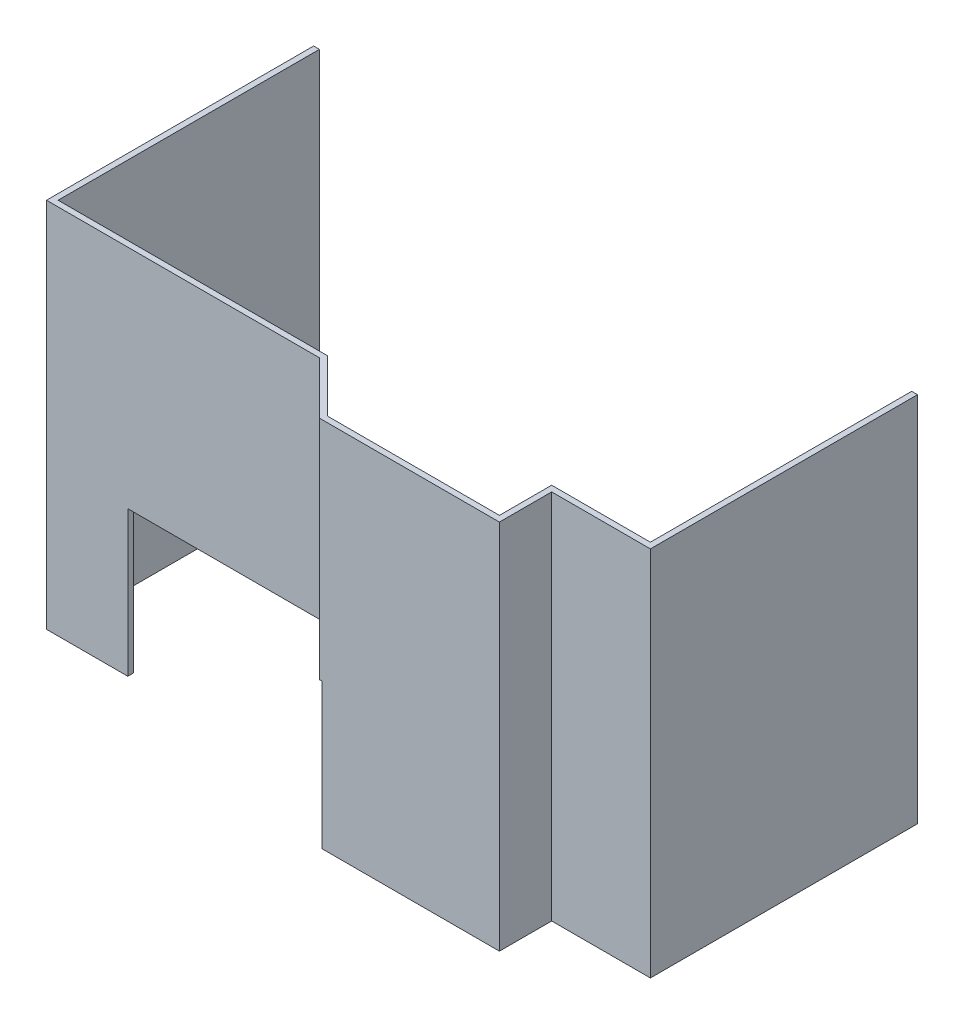
SolidWorks part; units mm, degrees
ref_plane "Front Plane" through (0, 0, 0) normal (0, 0, 1) x (1, 0, 0)
ref_plane "Top Plane" through (0, 0, 0) normal (0, 1, 0) x (1, 0, 0)
ref_plane "Right Plane" through (0, 0, 0) normal (1, 0, 0) x (0, 0, -1)
sketch "Sketch1" plane through (0, 0, 0) normal (0, 1, 0) x (1, 0, 0)
  line L0 (0, 0) -> (0, 292.1)
  line L1 (0, 292.1) -> (6.35, 292.1)
  line L2 (6.35, 292.1) -> (6.35, 6.35)
  line L3 (6.35, 6.35) -> (301.0803, 6.35)
  line L4 (0, 0) -> (298.45, 0)
  line L5 (298.45, 0) -> (355.6, -57.15)
  line L6 (355.6, -57.15) -> (552.45, -57.15)
  line L8 (552.45, 0) -> (660.4, 0)
  line L9 (660.4, 0) -> (660.4, 292.1)
  line L10 (660.4, 292.1) -> (654.05, 292.1)
  line L11 (654.05, 292.1) -> (654.05, 6.35)
  line L12 (654.05, 6.35) -> (546.1, 6.35)
  line L14 (546.1, -50.8) -> (358.2303, -50.8)
  line L15 (358.2303, -50.8) -> (301.0803, 6.35)
  line L16 (546.1, 6.35) -> (546.1, -50.8)
  line L17 (552.45, -57.15) -> (552.45, 0)
  dimension "D1" = 292.1
  dimension "D2" = 6.35
  dimension "D3" = 6.35
  dimension "D4" = 6.35
  dimension "D5" = 6.35
  dimension "D6" = 6.35
  dimension "D7" = 6.35
  dimension "D8" = 6.35
  dimension "D9" = 660.4
  dimension "D10" = 254
  dimension "D11" = 107.95
  dimension "D12" = 135
  dimension "D13" = 57.15
  dimension "D14" = 6.35
extrude "Boss-Extrude1" add sketch "Sketch1" along normal blind 406.4
sketch "Sketch2" plane through (0, 0, 57.15) normal (0, 0, 1) x (1, 0, 0)
  line L0 (355.6, 0) -> (552.45, 0) construction
  line L1 (358.2303, 0) -> (88.9, 0)
  line L2 (358.2303, 0) -> (358.2303, 158.75)
  line L3 (358.2303, 158.75) -> (88.9, 158.75)
  line L4 (88.9, 0) -> (88.9, 158.75)
  line L8 (358.2303, 406.4) -> (358.2303, 0) construction
  line L9 (0, 406.4) -> (0, 0) construction
  point P6 (0, 0)
  dimension "D1" = 158.75
  dimension "D2" = 88.9
extrude "Cut-Extrude1" cut sketch "Sketch2" against normal up to surface (63.5 mm away) up to face at (153.7151, 203.2, -6.35)
